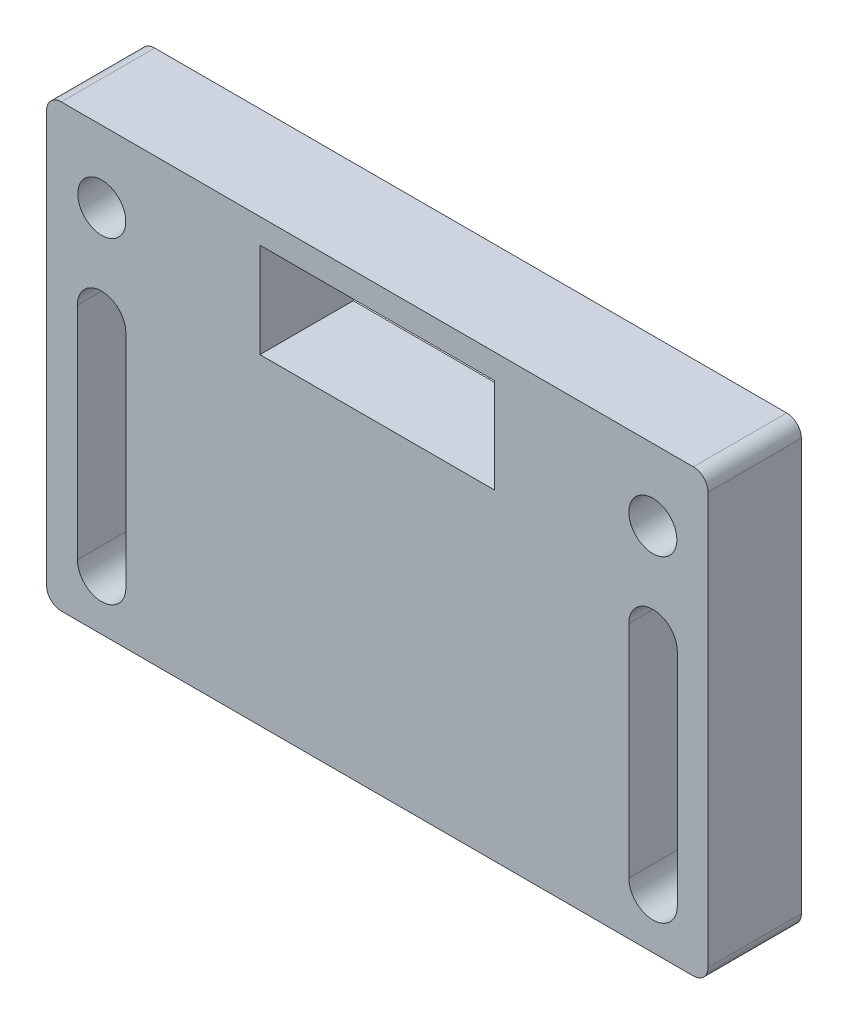
SolidWorks part; units mm, degrees
ref_plane "Front Plane" through (0, 0, 0) normal (0, 0, 1) x (1, 0, 0)
ref_plane "Top Plane" through (0, 0, 0) normal (0, 1, 0) x (1, 0, 0)
ref_plane "Right Plane" through (0, 0, 0) normal (1, 0, 0) x (0, 0, -1)
sketch "Sketch1" plane through (0, 0, 0) normal (0, 0, 1) x (1, 0, 0)
  line L0 (45, 0) -> (45, -60) construction
  line L1 (0, 0) -> (90, 0)
  line L2 (0, 0) -> (0, -60)
  line L3 (0, -60) -> (90, -60)
  line L4 (90, 0) -> (90, -60)
  line L5 (29.025, -3.3671) -> (29.025, -16.2671)
  line L6 (29.025, -16.2671) -> (60.975, -16.2671)
  line L7 (60.975, -16.2671) -> (60.975, -3.3671)
  line L9 (60.975, -3.3671) -> (45, -3.3671)
  line L10 (45, -3.3671) -> (29.025, -3.3671)
  dimension "D1" = 90
  dimension "D2" = 60
  dimension "D3" = 31.95
  dimension "D4" = 12.9
  dimension "D5" = 43.7329
extrude "Boss-Extrude1" add sketch "Sketch1" along normal blind 12.7
sketch "Sketch2" plane through (0, 0, 0) normal (0, 0, -1) x (-1, 0, 0)
  line L0 (-82.49, -9.7171) -> (-7.51, -9.7171) construction
  line L1 (0, -9.7171) -> (-7.51, -9.7171)
  line L2 (-90, -60) -> (-90, 0) construction
  line L3 (-90, -9.7171) -> (-82.49, -9.7171)
  line L4 (0, 0) -> (0, -60) construction
  dimension "D1" = 7.51
  dimension "D2" = 7.51
  dimension "D3" = 74.98
hole_wizard "CSK for 1/4 Flat Head Machine Screw1" positions "Sketch3" profile "Sketch4" countersink size "1/4" standard "ANSI Inch" end condition through all
sketch "Sketch3" plane through (0, 0, 0) normal (0, 0, -1) x (-1, 0, 0)
  point P0 (-82.49, -9.7171)
  point P3 (-7.51, -9.7171)
sketch "Sketch4" plane through (82.49, -9.7171, 0) normal (1, 0, 0) x (0, 1, 0)
  line L0 (0, 0) -> (0, 12.7)
  line L1 (0, 12.7) -> (3.2639, 12.7)
  line L2 (3.2639, 12.7) -> (3.2639, 3.6524)
  line L3 (3.2639, 3.6524) -> (6.4389, 0)
  line L5 (6.4389, 0) -> (0, 0)
  line L6 (-3.2639, 3.6524) -> (-6.4389, 0) construction
  line L11 (0, -6.35) -> (0, 107.95) construction
  dimension "Thru Hole Dia." = 6.5278
  dimension "Thru Hole Depth" = 12.7
  dimension "Near C'Sink Dia." = 12.8778
  dimension "Near C'Sink Angle" = 82
fillet "Fillet1" radius 2 4 edges at (0, -60, 6.35) (0, 0, 6.35) (90, 0, 6.35) (90, -60, 6.35)
sketch "Sketch5" plane through (0, 0, 0) normal (0, 0, -1) x (-1, 0, 0)
  line L0 (-10.785, -22.8474) -> (-10.785, -52.8474)
  line L1 (-4.185, -52.8474) -> (-4.185, -22.8474)
  line L2 (-10.785, -52.8474) -> (-79.215, -52.8474) construction
  line L3 (-79.215, -52.8474) -> (-79.215, -22.8474)
  line L4 (-85.815, -52.8474) -> (-85.815, -22.8474)
  line L5 (-85.815, -37.8474) -> (-90, -37.8474) construction
  line L6 (-2, -60) -> (-88, -60) construction
  line L7 (-90, -58) -> (-90, -2) construction
  line L8 (-4.185, -37.8474) -> (0, -37.8474) construction
  line L9 (-45, -46.606) -> (-45, 0) construction
  line L10 (-88, 0) -> (-2, 0) construction
  line L13 (0, -2) -> (0, -58) construction
  arc A0 (-10.785, -52.8474) -> (-4.185, -52.8474) centre (-7.485, -52.8474) ccw
  arc A1 (-4.185, -22.8474) -> (-10.785, -22.8474) centre (-7.485, -22.8474) ccw
  arc A2 (-85.815, -52.8474) -> (-79.215, -52.8474) centre (-82.515, -52.8474) ccw
  arc A3 (-79.215, -22.8474) -> (-85.815, -22.8474) centre (-82.515, -22.8474) ccw
  dimension "D1" = 3.3
  dimension "D4" = 3.3
  dimension "D7" = 7.1526
  dimension "D2" = 30
  dimension "D3" = 68.43
  dimension "D5" = 30
extrude "Cut-Extrude1" cut sketch "Sketch5" against normal through all
